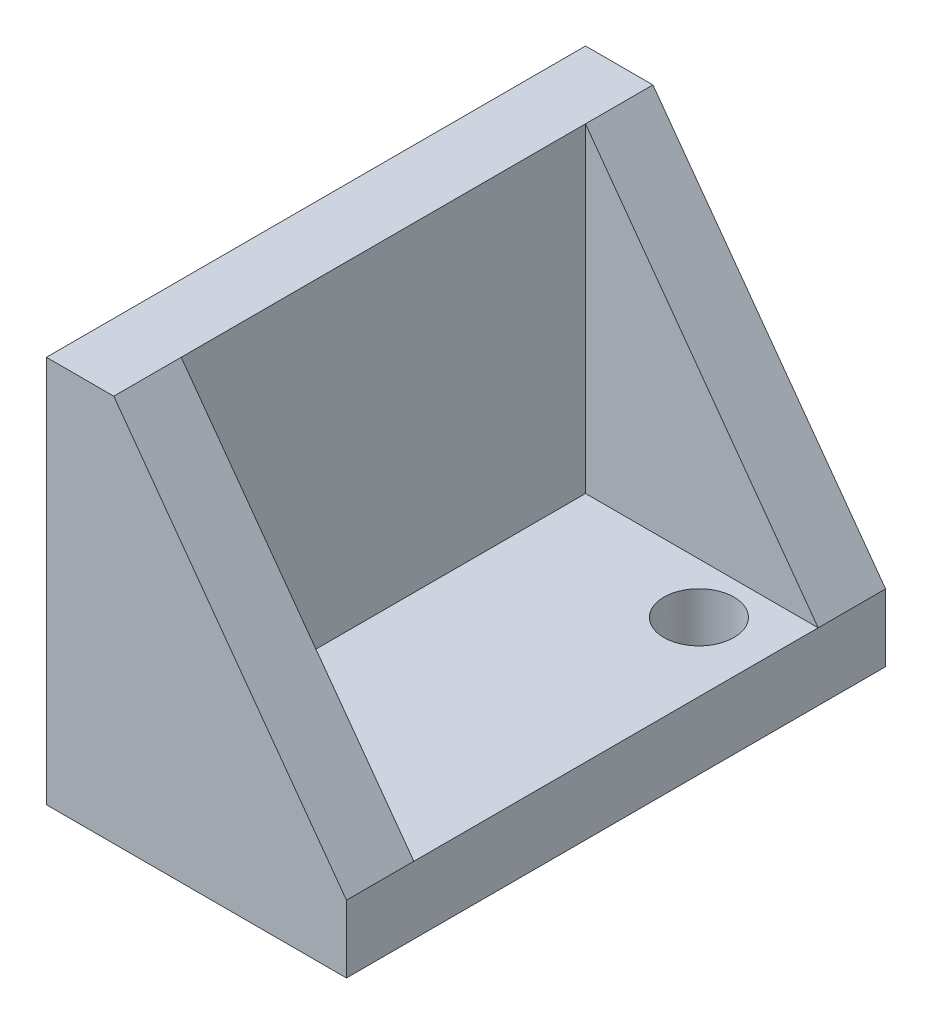
SolidWorks part; units mm, degrees
note: The reader was unsure of these and kept them because the rebuilt part matched: shared geometry of "Sketch3<2>".
material "6061-T6 (SS)"
ref_plane "Front Plane" through (0, 0, 0) normal (0, 0, 1) x (1, 0, 0)
ref_plane "Top Plane" through (0, 0, 0) normal (0, 1, 0) x (1, 0, 0)
ref_plane "Right Plane" through (0, 0, 0) normal (1, 0, 0) x (0, 0, -1)
sketch "Sketch1" plane through (0, 0, 0) normal (0, 0, 1) x (1, 0, 0)
  line L0 (152.5271, 81.5316) -> (152.5271, 87.8816) construction
  line L1 (124.254, 81.5316) -> (152.5271, 81.5316) construction
  line L2 (124.254, 81.5316) -> (124.254, 118.0483) construction
  line L3 (124.254, 118.0483) -> (130.604, 118.0483) construction
  line L4 (130.604, 118.0483) -> (130.604, 87.8816) construction
  line L5 (152.5271, 87.8816) -> (130.604, 87.8816) construction
  line L6 (152.5271, 81.5316) -> (152.5271, 87.8816)
  line L7 (124.254, 81.5316) -> (152.5271, 81.5316)
  line L8 (124.254, 81.5316) -> (124.254, 118.0483)
  line L9 (124.254, 118.0483) -> (130.604, 118.0483)
  line L10 (130.604, 118.0483) -> (130.604, 87.8816)
  line L11 (152.5271, 87.8816) -> (130.604, 87.8816)
extrude "Boss-Extrude1" add sketch "Sketch1" against normal up to vertex from vertex
sketch "Sketch2" plane through (0, 0, 0) normal (0, 1, 0) x (1, 0, 0)
  circle A0 centre (146.0501, -1068.1253) radius 3.302 construction
  circle A1 centre (146.0501, -1068.1253) radius 3.302
extrude "Cut-Extrude1" cut sketch "Sketch2" against normal through all both and the other way through all
sketch "Sketch3" plane through (0, 0, 0) normal (0, 0, 1) x (1, 0, 0)
  line L0 (130.604, 118.0483) -> (152.5271, 87.8816) construction
  line L1 (130.604, 118.0483) -> (130.604, 87.8816) construction
  line L2 (152.5271, 87.8816) -> (130.604, 87.8816) construction
  line L3 (130.604, 118.0483) -> (152.5271, 87.8816)
  line L4 (130.604, 118.0483) -> (130.604, 87.8816)
  line L5 (152.5271, 87.8816) -> (130.604, 87.8816)
extrude "Boss-Extrude2" add sketch "Sketch3" along normal up to vertex from vertex
extrude "Boss-Extrude3" add sketch "Sketch3<2>" along normal up to vertex from vertex
sketch "Sketch3<2>" plane through (0, 0, 0) normal (0, 0, 1) x (1, 0, 0) same geometry as "Sketch3"
